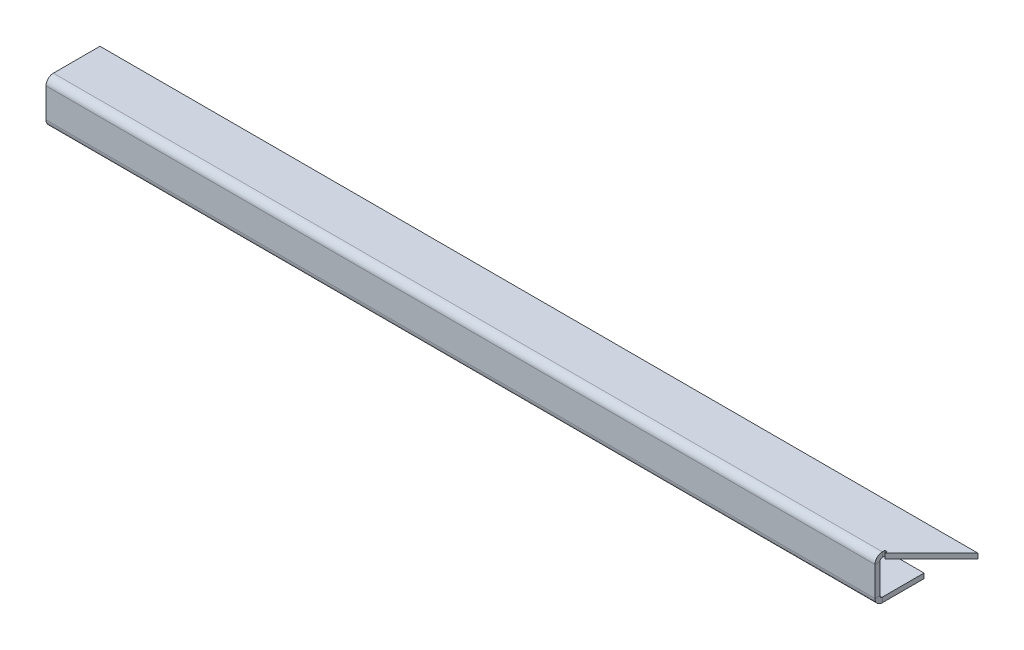
SolidWorks part; units mm, degrees
note: The reader was unsure of these and kept them because the rebuilt part matched: flange length of "Edge-Flange1", "Edge-Flange2".
material "St.37"
ref_plane "Front Plane" through (0, 0, 0) normal (0, 0, 1) x (1, 0, 0)
ref_plane "Top Plane" through (0, 0, 0) normal (0, 1, 0) x (1, 0, 0)
ref_plane "Right Plane" through (0, 0, 0) normal (1, 0, 0) x (0, 0, -1)
sketch "Sketch1" plane through (0, 0, 0) normal (0, 1, 0) x (1, 0, 0)
  line L0 (-84.5, 0) -> (84.5, 0)
  line L2 (84.5, 0) -> (94.5, 10)
  line L3 (-84.5, 10) -> (94.5, 10)
  line L4 (-84.5, 0) -> (-84.5, 10)
  point P3 (0, 0)
  dimension "D1" = 169
  dimension "D2" = 225
  dimension "D3" = 10
base flange "Base-Flange1" sketch "Sketch1" thickness 1 reverse thickness direction no parameters "D1"=1
edge flange "Edge-Flange1" sketch "Sketch8" flange angle 90 flange length 8 flange position material outside bend radius 0.5 thickness 1 relief rectangular parameters "D6"=10
sketch "Sketch8" plane through (0, -1, 0) normal (0, 0, 1) x (-1, 0, 0)
  line L2 (-84.5, 0) -> (-84.5, 7)
  line L3 (-84.5, 7) -> (84.5, 7)
  line L4 (84.5, 7) -> (84.5, 0)
  line L7 (84.5, 0) -> (-84.5, 0) construction
  line L8 (84.5, 0) -> (-84.5, 0)
bend "EdgeBend1" bend radius 0.5 bend angle 90 parameters "D5"=1
edge flange "Edge-Flange2" sketch "Sketch11" flange angle 90 flange length 10 flange position material outside bend radius 0.5 thickness 1 relief rectangular parameters "D6"=10
sketch "Sketch11" plane through (0, -8, 0) normal (0, -1, 0) x (-1, 0, 0)
  line L2 (-84.5, 0) -> (-84.5, 9)
  line L3 (-84.5, 9) -> (84.5, 9)
  line L4 (84.5, 9) -> (84.5, 0)
  line L7 (84.5, 0) -> (-84.5, 0) construction
  line L8 (84.5, 0) -> (-84.5, 0)
bend "EdgeBend2" bend radius 0.5 bend angle 90 parameters "D5"=2
sketch "Sketch12" plane through (0, -9, 0) normal (0, -1, 0) x (1, 0, 0)
  line L0 (-84.5, -0.5) -> (-84.5, -9) construction
  line L1 (-84.5, -9) -> (84.5, -9) construction
  line L2 (84.5, -9) -> (84.5, -0.5) construction
  circle A0 centre (-74.5, -5) radius 1.5
  circle A1 centre (0, -5) radius 1.5
  circle A2 centre (74.5, -5) radius 1.5
  dimension "D2" = 3
  dimension "D1" = 10
  dimension "D3" = 4
  dimension "D5" = 10
  dimension "D4" = 3
extrude "Cut-Extrude1" cut sketch "Sketch12" against normal blind 3 normal cut yes
sketch "Bend-Lines1" [suppressed] plane through (0, 0, 0) normal (0, 1, 0) x (1, 0, 0)
sketch "Bounding-Box1" [suppressed] plane through (0, 0, 0) normal (0, 1, 0) x (1, 0, 0)
sheet metal parameters "Sheet-Metal1" thickness 1 parameters "D1"=1
flat pattern "Flat-Pattern1" [suppressed]
sketch "Bend-Lines2" plane through (0, 0, 0) normal (0, 1, 0) x (1, 0, 0)
sketch3d "Bounding-Box2" [suppressed]
  line L0 (-70, 10, 0) -> (70, 10, 0) construction
  line L1 (-70, 0, 0) -> (70, 0, 0) construction
  line L2 (-70, 10, 0) -> (-70, 0, 0) construction
  line L3 (70, 10, 0) -> (70, 0, 0) construction
sheet metal parameters "Sheet-Metal2" thickness 1 parameters "D1"=1
flat pattern "Flat-Pattern1"
sketch "Bend-Lines2" plane through (0, 0, 0) normal (0, 1, 0) x (1, 0, 0)
  line L0 (-60, -0.2854) -> (60, -0.2854) construction
  line L1 (-60, -0.2854) -> (60, -0.2854) construction
sketch3d "Bounding-Box2" [suppressed]
  line L0 (70, 10, 0) -> (-70, 10, 0) construction
  line L1 (70, -7.5708, 0) -> (-70, -7.5708, 0) construction
  line L2 (70, 10, 0) -> (70, -7.5708, 0) construction
  line L3 (-70, 10, 0) -> (-70, -7.5708, 0) construction
bend of the flat pattern "Flatten-<EdgeBend1>1"
sheet metal parameters "Sheet-Metal3" thickness 1 parameters "D1"=1
flat pattern "Flat-Pattern1"
sketch "Bend-Lines2" plane through (0, 0, 0) normal (0, 1, 0) x (1, 0, 0)
  line L0 (-60, -0.2854) -> (60, -0.2854) construction
  line L1 (-60, -0.2854) -> (60, -0.2854) construction
  line L2 (-60, -7.7489) -> (60, -7.7489) construction
  line L3 (-60, -7.7489) -> (60, -7.7489) construction
sketch3d "Bounding-Box2" [suppressed]
  line L0 (70, 10, 0) -> (-70, 10, 0) construction
  line L1 (70, -16.927, 0) -> (-70, -16.927, 0) construction
  line L2 (70, 10, 0) -> (70, -16.927, 0) construction
  line L3 (-70, 10, 0) -> (-70, -16.927, 0) construction
bend of the flat pattern "Flatten-<EdgeBend1>1"
bend of the flat pattern "Flatten-<EdgeBend2>1"
sheet metal parameters "Sheet-Metal4" thickness 1 parameters "D1"=1
flat pattern "Flat-Pattern1"
sketch "Bend-Lines2" plane through (0, 0, 0) normal (0, 1, 0) x (1, 0, 0)
  line L0 (-84.5, -0.2854) -> (84.5, -0.2854) construction
  line L1 (-84.5, -0.2854) -> (84.5, -0.2854) construction
  line L2 (-84.5, -7.8562) -> (84.5, -7.8562) construction
  line L3 (-84.5, -7.8562) -> (84.5, -7.8562) construction
sketch3d "Bounding-Box2" [suppressed]
  line L0 (94.5, 10, 0) -> (-84.5, 10, 0) construction
  line L1 (94.5, -17.1416, 0) -> (-84.5, -17.1416, 0) construction
  line L2 (94.5, 10, 0) -> (94.5, -17.1416, 0) construction
  line L3 (-84.5, 10, 0) -> (-84.5, -17.1416, 0) construction
bend of the flat pattern "Flatten-<EdgeBend1>1"
bend of the flat pattern "Flatten-<EdgeBend2>1"
